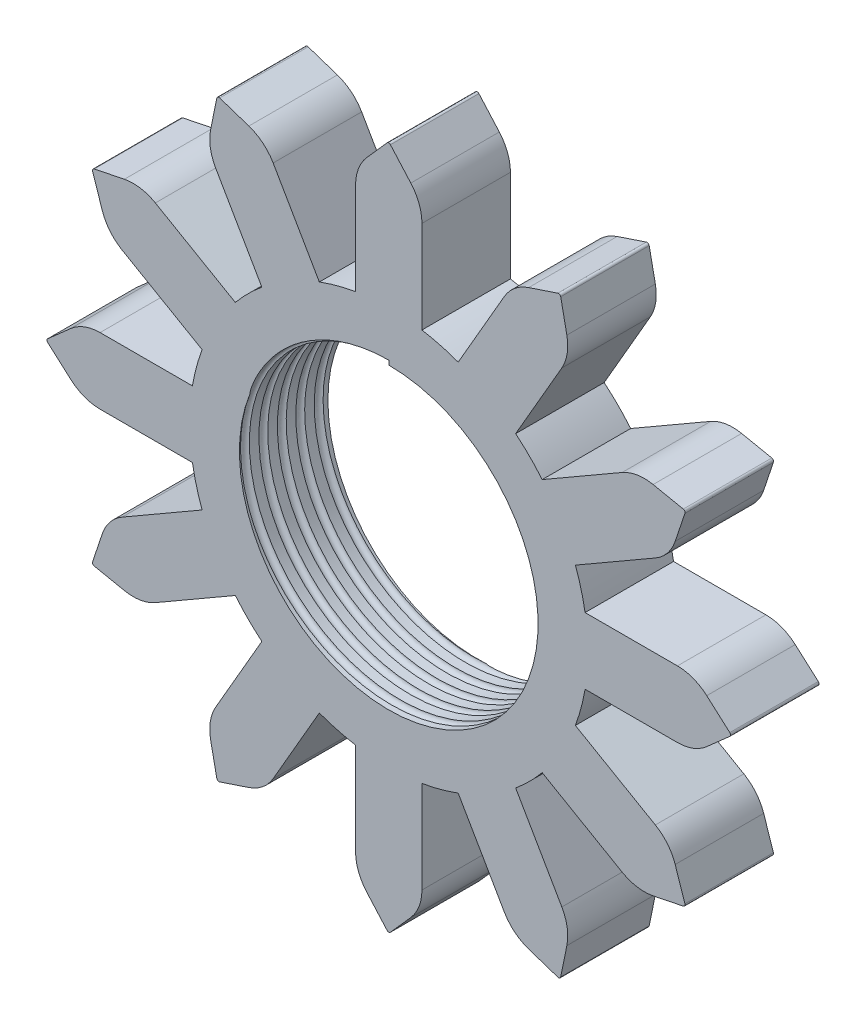
SolidWorks part; units mm, degrees
ref_plane "Front Plane" through (0, 0, 0) normal (0, 0, 1) x (1, 0, 0)
ref_plane "Top Plane" through (0, 0, 0) normal (0, 1, 0) x (1, 0, 0)
ref_plane "Right Plane" through (0, 0, 0) normal (1, 0, 0) x (0, 0, -1)
sketch "Sketch1" plane through (0, 0, 0) normal (0, 0, 1) x (1, 0, 0)
  line L0 (-0.0749, 15.4155) -> (-0.9972, 14.3741)
  line L1 (-1.5, 13.0481) -> (-1.5, 8.8741)
  line L2 (0, 15.5) -> (0, 9) construction
  line L3 (0.0749, 15.4155) -> (0.9972, 14.3741)
  line L4 (1.5, 13.0481) -> (1.5, 8.8741)
  line L5 (13.0481, 1.5) -> (8.8741, 1.5)
  line L6 (15.4155, 0.0749) -> (14.3741, 0.9972)
  line L7 (15.4155, -0.0749) -> (14.3741, -0.9972)
  line L8 (13.0481, -1.5) -> (8.8741, -1.5)
  line L9 (1.5, -13.0481) -> (1.5, -8.8741)
  line L10 (0.0749, -15.4155) -> (0.9972, -14.3741)
  line L11 (-0.0749, -15.4155) -> (-0.9972, -14.3741)
  line L12 (-1.5, -13.0481) -> (-1.5, -8.8741)
  line L13 (-13.0481, -1.5) -> (-8.8741, -1.5)
  line L14 (-15.4155, -0.0749) -> (-14.3741, -0.9972)
  line L15 (-15.4155, 0.0749) -> (-14.3741, 0.9972)
  line L16 (-13.0481, 1.5) -> (-8.8741, 1.5)
  line L17 (5.225, 12.05) -> (3.138, 8.4352)
  line L18 (7.6429, 13.3876) -> (6.3235, 12.9469)
  line L19 (7.7726, 13.3128) -> (8.0507, 11.9498)
  line L20 (7.8231, 10.55) -> (5.7361, 6.9352)
  line L21 (10.55, 7.8231) -> (6.9352, 5.7361)
  line L22 (13.3128, 7.7726) -> (11.9498, 8.0507)
  line L23 (13.3876, 7.6429) -> (12.9469, 6.3235)
  line L24 (12.05, 5.225) -> (8.4352, 3.138)
  line L25 (13.0481, 1.5) -> (8.8741, 1.5)
  line L26 (15.4155, 0.0749) -> (14.3741, 0.9972)
  line L27 (15.4155, -0.0749) -> (14.3741, -0.9972)
  line L28 (13.0481, -1.5) -> (8.8741, -1.5)
  line L29 (12.05, -5.225) -> (8.4352, -3.138)
  line L30 (13.3876, -7.6429) -> (12.9469, -6.3235)
  line L31 (13.3128, -7.7726) -> (11.9498, -8.0507)
  line L32 (10.55, -7.8231) -> (6.9352, -5.7361)
  line L33 (7.8231, -10.55) -> (5.7361, -6.9352)
  line L34 (7.7726, -13.3128) -> (8.0507, -11.9498)
  line L35 (7.6429, -13.3876) -> (6.3235, -12.9469)
  line L36 (5.225, -12.05) -> (3.138, -8.4352)
  line L37 (1.5, -13.0481) -> (1.5, -8.8741)
  line L38 (0.0749, -15.4155) -> (0.9972, -14.3741)
  line L39 (-0.0749, -15.4155) -> (-0.9972, -14.3741)
  line L40 (-1.5, -13.0481) -> (-1.5, -8.8741)
  line L41 (-5.225, -12.05) -> (-3.138, -8.4352)
  line L42 (-7.6429, -13.3876) -> (-6.3235, -12.9469)
  line L43 (-7.7726, -13.3128) -> (-8.0507, -11.9498)
  line L44 (-7.8231, -10.55) -> (-5.7361, -6.9352)
  line L45 (-10.55, -7.8231) -> (-6.9352, -5.7361)
  line L46 (-13.3128, -7.7726) -> (-11.9498, -8.0507)
  line L47 (-13.3876, -7.6429) -> (-12.9469, -6.3235)
  line L48 (-12.05, -5.225) -> (-8.4352, -3.138)
  line L49 (-13.0481, -1.5) -> (-8.8741, -1.5)
  line L50 (-15.4155, -0.0749) -> (-14.3741, -0.9972)
  line L51 (-15.4155, 0.0749) -> (-14.3741, 0.9972)
  line L52 (-13.0481, 1.5) -> (-8.8741, 1.5)
  line L53 (-12.05, 5.225) -> (-8.4352, 3.138)
  line L54 (-13.3876, 7.6429) -> (-12.9469, 6.3235)
  line L55 (-13.3128, 7.7726) -> (-11.9498, 8.0507)
  line L56 (-10.55, 7.8231) -> (-6.9352, 5.7361)
  line L57 (-7.8231, 10.55) -> (-5.7361, 6.9352)
  line L58 (-7.7726, 13.3128) -> (-8.0507, 11.9498)
  line L59 (-7.6429, 13.3876) -> (-6.3235, 12.9469)
  line L60 (-5.225, 12.05) -> (-3.138, 8.4352)
  circle A0 centre (0, 0) radius 6.75
  circle A1 centre (0, 0) radius 9
  arc A2 (1.5, 13.0481) -> (0.9972, 14.3741) centre (-0.5, 13.0481) ccw
  arc A3 (-1.5, 13.0481) -> (-0.9972, 14.3741) centre (0.5, 13.0481) cw
  arc A4 (0.0749, 15.4155) -> (-0.0749, 15.4155) centre (0, 15.3492) ccw
  arc A5 (13.0481, 1.5) -> (14.3741, 0.9972) centre (13.0481, -0.5) cw
  arc A6 (15.4155, -0.0749) -> (15.4155, 0.0749) centre (15.3492, 0) ccw
  arc A7 (13.0481, -1.5) -> (14.3741, -0.9972) centre (13.0481, 0.5) ccw
  arc A8 (1.5, -13.0481) -> (0.9972, -14.3741) centre (-0.5, -13.0481) cw
  arc A9 (-0.0749, -15.4155) -> (0.0749, -15.4155) centre (0, -15.3492) ccw
  arc A10 (-1.5, -13.0481) -> (-0.9972, -14.3741) centre (0.5, -13.0481) ccw
  arc A11 (-13.0481, -1.5) -> (-14.3741, -0.9972) centre (-13.0481, 0.5) cw
  arc A12 (-15.4155, 0.0749) -> (-15.4155, -0.0749) centre (-15.3492, 0) ccw
  arc A13 (-13.0481, 1.5) -> (-14.3741, 0.9972) centre (-13.0481, -0.5) ccw
  arc A14 (5.225, 12.05) -> (6.3235, 12.9469) centre (6.957, 11.05) cw
  arc A15 (7.7726, 13.3128) -> (7.6429, 13.3876) centre (7.6746, 13.2928) ccw
  arc A16 (7.8231, 10.55) -> (8.0507, 11.9498) centre (6.091, 11.55) ccw
  arc A17 (10.55, 7.8231) -> (11.9498, 8.0507) centre (11.55, 6.091) cw
  arc A18 (13.3876, 7.6429) -> (13.3128, 7.7726) centre (13.2928, 7.6746) ccw
  arc A19 (12.05, 5.225) -> (12.9469, 6.3235) centre (11.05, 6.957) ccw
  arc A20 (13.0481, 1.5) -> (14.3741, 0.9972) centre (13.0481, -0.5) cw
  arc A21 (15.4155, -0.0749) -> (15.4155, 0.0749) centre (15.3492, 0) ccw
  arc A22 (13.0481, -1.5) -> (14.3741, -0.9972) centre (13.0481, 0.5) ccw
  arc A23 (12.05, -5.225) -> (12.9469, -6.3235) centre (11.05, -6.957) cw
  arc A24 (13.3128, -7.7726) -> (13.3876, -7.6429) centre (13.2928, -7.6746) ccw
  arc A25 (10.55, -7.8231) -> (11.9498, -8.0507) centre (11.55, -6.091) ccw
  arc A26 (7.8231, -10.55) -> (8.0507, -11.9498) centre (6.091, -11.55) cw
  arc A27 (7.6429, -13.3876) -> (7.7726, -13.3128) centre (7.6746, -13.2928) ccw
  arc A28 (5.225, -12.05) -> (6.3235, -12.9469) centre (6.957, -11.05) ccw
  arc A29 (1.5, -13.0481) -> (0.9972, -14.3741) centre (-0.5, -13.0481) cw
  arc A30 (-0.0749, -15.4155) -> (0.0749, -15.4155) centre (0, -15.3492) ccw
  arc A31 (-1.5, -13.0481) -> (-0.9972, -14.3741) centre (0.5, -13.0481) ccw
  arc A32 (-5.225, -12.05) -> (-6.3235, -12.9469) centre (-6.957, -11.05) cw
  arc A33 (-7.7726, -13.3128) -> (-7.6429, -13.3876) centre (-7.6746, -13.2928) ccw
  arc A34 (-7.8231, -10.55) -> (-8.0507, -11.9498) centre (-6.091, -11.55) ccw
  arc A35 (-10.55, -7.8231) -> (-11.9498, -8.0507) centre (-11.55, -6.091) cw
  arc A36 (-13.3876, -7.6429) -> (-13.3128, -7.7726) centre (-13.2928, -7.6746) ccw
  arc A37 (-12.05, -5.225) -> (-12.9469, -6.3235) centre (-11.05, -6.957) ccw
  arc A38 (-13.0481, -1.5) -> (-14.3741, -0.9972) centre (-13.0481, 0.5) cw
  arc A39 (-15.4155, 0.0749) -> (-15.4155, -0.0749) centre (-15.3492, 0) ccw
  arc A40 (-13.0481, 1.5) -> (-14.3741, 0.9972) centre (-13.0481, -0.5) ccw
  arc A41 (-12.05, 5.225) -> (-12.9469, 6.3235) centre (-11.05, 6.957) cw
  arc A42 (-13.3128, 7.7726) -> (-13.3876, 7.6429) centre (-13.2928, 7.6746) ccw
  arc A43 (-10.55, 7.8231) -> (-11.9498, 8.0507) centre (-11.55, 6.091) ccw
  arc A44 (-7.8231, 10.55) -> (-8.0507, 11.9498) centre (-6.091, 11.55) cw
  arc A45 (-7.6429, 13.3876) -> (-7.7726, 13.3128) centre (-7.6746, 13.2928) ccw
  arc A46 (-5.225, 12.05) -> (-6.3235, 12.9469) centre (-6.957, 11.05) ccw
  point P12 (1.5, 13.8064)
  point P15 (-1.5, 13.8064)
  point P55 (0, 0)
  point P176 (0, 0)
  dimension "D1" = 18
  dimension "D2" = 13.5
  dimension "D6" = 2
  dimension "D7" = 0.1
  dimension "D3" = 6.5
  dimension "D4" = 1.5
  dimension "D5" = 5.5
extrude "Boss-Extrude1" add sketch "Sketch1" along normal blind 4
sketch "Sketch2" plane through (0, 0, 0) normal (0, 0, 1) x (1, 0, 0)
  circle A0 centre (0, 0) radius 6.75
  dimension "D1" = 13.5
curve "Helix/Spiral1" pitch 0.8333 height 3.9583 turns 4.75
sketch "Sketch4" plane through (0, 0, 0) normal (1, 0, 0) x (0, 0, -1)
  circle A0 centre (-0.2083, -6.75) radius 0.2
  dimension "D1" = 0.4
sweep "Cut-Sweep8" cut profiles "Sketch4" path "Helix/Spiral1"
sketch "Sketch5" plane through (0, 0, 4) normal (0, 0, 1) x (1, 0, 0)
  circle A0 centre (0, 0) radius 9
  arc A1 (-8.4352, 3.138) -> (-8.8741, 1.5) centre (0, 0) ccw construction
